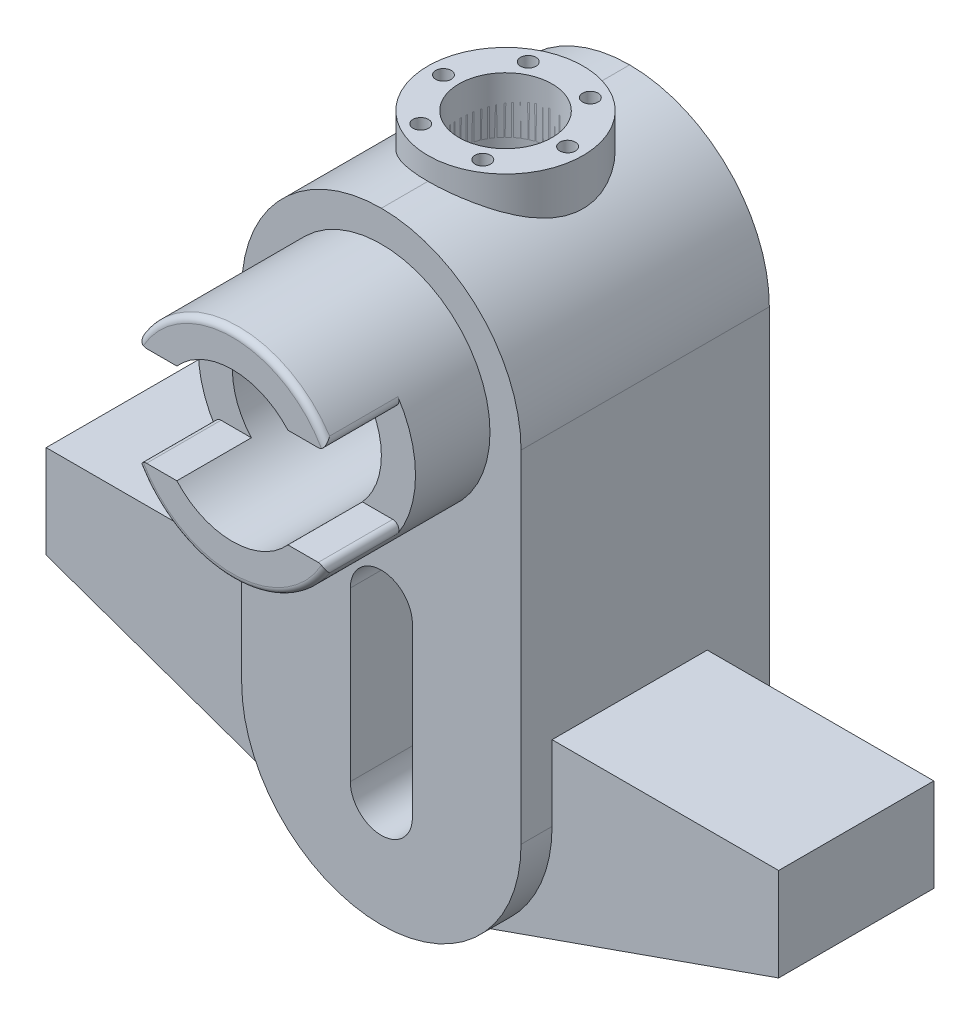
SolidWorks part; units mm, degrees
ref_plane "정면" through (0, 0, 0) normal (0, 0, 1) x (1, 0, 0)
ref_plane "윗면" through (0, 0, 0) normal (0, 1, 0) x (1, 0, 0)
ref_plane "우측면" through (0, 0, 0) normal (1, 0, 0) x (0, 0, -1)
sketch "스케치1" plane through (0, 0, 0) normal (0, 0, 1) x (1, 0, 0)
  line L1 (-22.5, 50) -> (22.5, 50)
  line L2 (-22.5, 50) -> (-22.5, -50)
  line L3 (-22.5, -50) -> (22.5, -50)
  line L4 (22.5, 50) -> (22.5, -50)
  line L5 (-22.5, 50) -> (22.5, -50) construction
  line L6 (-22.5, -50) -> (22.5, 50) construction
  point P0 (0, 0)
  dimension "D1" = 45
  dimension "D2" = 100
extrude "보스-돌출1" add sketch "스케치1" along normal blind 40
fillet "필렛1" radius 22.5 4 edges at (22.5, -50, 20) (-22.5, -50, 20) (22.5, 50, 20) (-22.5, 50, 20)
sketch "스케치2" plane through (0, 0, 40) normal (0, 0, 1) x (1, 0, 0)
  circle A0 centre (0, 27.5) radius 17.5
  dimension "D1" = 35
extrude "보스-돌출2" add sketch "스케치2" along normal blind 24
sketch "스케치4" plane through (0, 0, 0) normal (0, 0, -1) x (-1, 0, 0)
  circle A0 centre (0, 27.5) radius 12
  dimension "D1" = 24
extrude "컷-돌출2" cut sketch "스케치4" against normal through all
sketch "스케치5" plane through (0, 0, 64) normal (0, 0, 1) x (1, 0, 0)
  line L1 (-31.1567, 35.5) -> (31.1567, 35.5)
  line L2 (-31.1567, 35.5) -> (-31.1567, 19.5)
  line L3 (-31.1567, 19.5) -> (31.1567, 19.5)
  line L4 (31.1567, 35.5) -> (31.1567, 19.5)
  line L5 (-31.1567, 35.5) -> (31.1567, 19.5) construction
  line L6 (-31.1567, 19.5) -> (31.1567, 35.5) construction
  point P0 (0, 27.5)
  dimension "D1" = 16
sketch "스케치7" plane through (0, 0, 0) normal (0, 0, 1) x (1, 0, 0)
  line L0 (-22.5, -15.3991) -> (-59, -15.3991)
  line L1 (-22.5, 27.5) -> (-22.5, -27.5) construction
  line L2 (-59, -15.3991) -> (-59, -30.3991)
  line L3 (-59, -30.3991) -> (-10.0464, -47.6325)
  line L4 (-22.5, -15.3991) -> (-22.5, -27.5)
  arc A0 (-22.5, -27.5) -> (0, -50) centre (0, -27.5) ccw construction
  arc A1 (-22.5, -27.5) -> (-10.0464, -47.6325) centre (0, -27.5) ccw
  dimension "D1" = 15
  dimension "D2" = 59
extrude "보스-돌출4" add sketch "스케치7" along normal blind 25 from offset 10 contours L0 L2 L3 A1 L4
ref_plane "평면1" through (0, 0, 0) normal (-1, 0, 0) x (0, 0, 1)
mirror "대칭 복사1" about plane through (0, 0, 0) normal (-1, 0, 0) of "보스-돌출4"
extrude "컷-돌출5" cut sketch "스케치5" against normal blind 12 contours L1 L4 L3 L2
ref_plane "평면4" through (0, 44.6009, 0) normal (0, 1, 0) x (1, 0, 0)
sketch "스케치12" plane through (0, 44.6009, 0) normal (0, 1, 0) x (1, 0, 0)
  line L0 (0, 0) -> (0, -40) construction
  circle A0 centre (0, -20) radius 12.5
  dimension "D1" = 25
extrude "보스-돌출9" add sketch "스케치12" along normal blind 9 separate body
sketch "스케치13" plane through (0, 53.6009, 0) normal (0, 1, 0) x (1, 0, 0)
  circle A0 centre (0, -20) radius 7.5
  dimension "D1" = 15
extrude "컷-돌출6" cut sketch "스케치13" against normal blind 15
sketch "스케치18" plane through (0, 0, 40) normal (0, 0, 1) x (1, 0, 0)
  line L0 (0, -5.4898) -> (0, -32.5) construction
  line L1 (5, -5.4898) -> (5, -32.5)
  line L2 (-5, -5.4898) -> (-5, -32.5)
  arc A0 (5, -5.4898) -> (-5, -5.4898) centre (0, -5.4898) ccw
  arc A1 (-5, -32.5) -> (5, -32.5) centre (0, -32.5) ccw
  point P3 (0, -18.9949)
  point P8 (0, 27.5)
  dimension "D1" = 60
  dimension "D2" = 10
extrude "컷-돌출7" cut sketch "스케치18" against normal through all
ref_plane "평면5" through (0, 54.6009, 0) normal (0, 1, 0) x (1, 0, 0)
sketch "스케치20" plane through (0, 54.6009, 0) normal (0, 1, 0) x (1, 0, 0)
  line L0 (0, -20) -> (-25.2088, -20) construction
  line L1 (-25.2088, -20) -> (22.5, -20) construction
  line L2 (22.5, -35) -> (22.5, -10) construction
  line L3 (0, 0) -> (0, -40) construction
  line L4 (-17.5, -40) -> (17.5, -40) construction
  circle A0 centre (0, -20) radius 10
  point P12 (-10, -20)
  point P13 (10, -20)
  dimension "D1" = 20
hole_wizard "M3 나사 구멍2" positions "3D스케치4" profile "스케치21" tap size "M3" standard "KS"
sketch3d "3D스케치4"
  point P0 (-10, 54.6009, 20)
cosmetic thread "구멍 나사산2" parameters "D1"=6, "D2"=3
sketch "스케치21" plane through (-10, 54.6009, 20) normal (1, 0, 0) x (0, 0, 1)
  line L0 (0, 0) -> (0, 6.7511)
  line L1 (0, 6.7511) -> (1.25, 6)
  line L2 (1.25, 6) -> (1.25, 0.2656)
  line L3 (1.25, 0.2656) -> (1.525, 0)
  line L5 (1.525, 0) -> (0, 0)
  line L6 (-1.25, 0.2656) -> (-1.525, 0) construction
  line L10 (0, 6.7511) -> (-1.25, 6) construction
  line L11 (0, -6.35) -> (0, 107.95) construction
  dimension "탭 드릴 지름" = 2.5
  dimension "탭 드릴 깊이" = 6
  dimension "표면 카운터싱크 지름" = 3.05
  dimension "표면 카운터싱크 각도" = 92
  dimension "드릴 각도" = 118
pattern_circular "원형 패턴2" count 6 over 360 about axis through (0, 53.6009, 20) along (0, 1, 0) of "M3 나사 구멍2"
fillet "필렛2" radius 1 6 edges at (0, 10, 64) (0, 45, 64) (15.5644, 35.5, 58) (-15.5644, 35.5, 58) (-15.5644, 19.5, 58) (15.5644, 19.5, 58)
